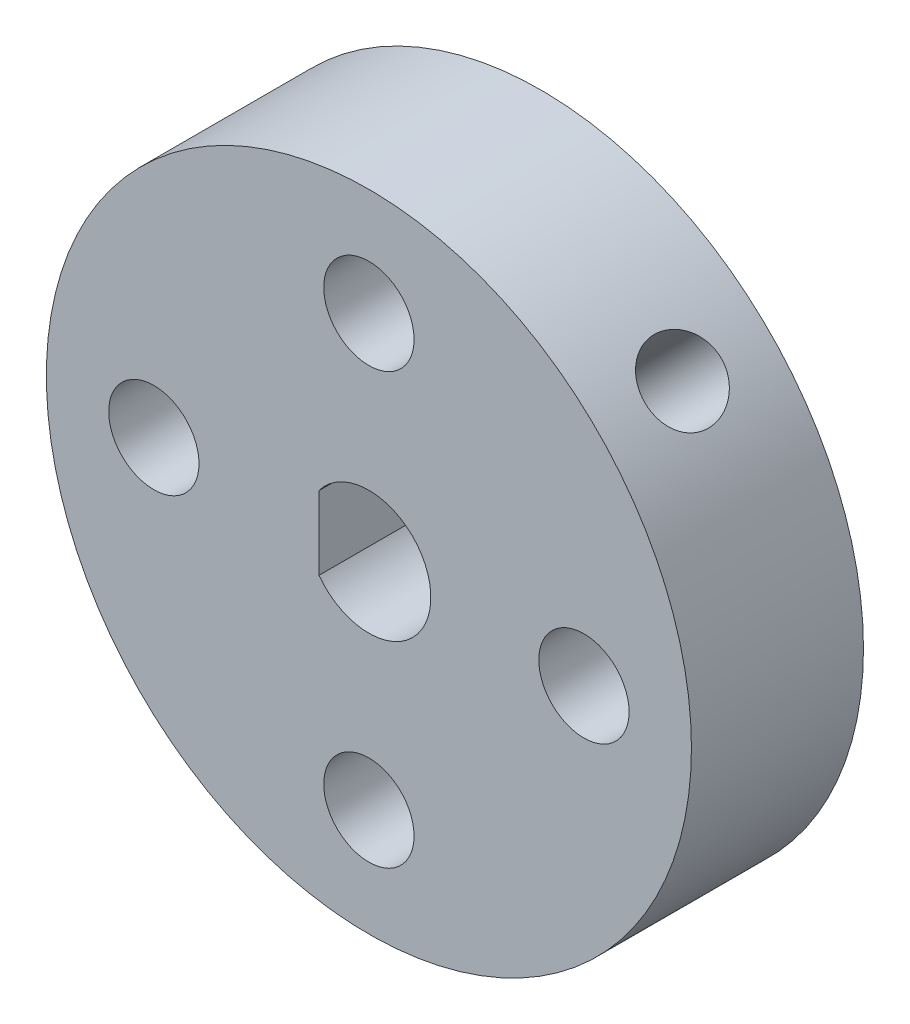
SolidWorks part; units mm, degrees
ref_plane "Front Plane" through (0, 0, 0) normal (0, 0, 1) x (1, 0, 0)
ref_plane "Top Plane" through (0, 0, 0) normal (0, 1, 0) x (1, 0, 0)
ref_plane "Right Plane" through (0, 0, 0) normal (1, 0, 0) x (0, 0, -1)
sketch "Sketch1" plane through (0, 0, 0) normal (0, 0, 1) x (1, 0, 0)
  line L0 (0, 0) -> (6.7352, 6.7352) construction
  line L1 (6.7352, 6.7352) -> (6.35, 0) construction
  line L2 (6.35, 0) -> (6.7352, 6.7352) construction
  line L3 (6.7352, 6.7352) -> (0, 6.35) construction
  line L4 (-1.4732, 1.0836) -> (-1.4732, -1.0836)
  circle A0 centre (0, 0) radius 9.525
  arc A1 (-1.4732, -1.0836) -> (-1.4732, 1.0836) centre (0, 0) ccw
  circle A2 centre (-6.35, 0) radius 1.3335
  circle A3 centre (0, 6.35) radius 1.3335
  circle A4 centre (6.35, 0) radius 1.3335
  circle A5 centre (0, -6.35) radius 1.3335
  point P3 (0, 0)
  point P15 (1.8288, 0)
  dimension "D1" = 19.05
  dimension "D2" = 3.6576
  dimension "D4" = 2.667
  dimension "D3" = 6.35
  dimension "D6" = 3.302
  dimension "D5" = 4
extrude "Boss-Extrude1" add sketch "Sketch1" along normal blind 5.08
ref_plane "Plane1" through (6.7352, 6.7352, 0) normal (0.7071, 0.7071, 0) x (-0.7071, 0.7071, 0)
sketch "Sketch2" plane through (6.7352, 6.7352, 0) normal (0.7071, 0.7071, 0) x (-0.7071, 0.7071, 0)
  circle A0 centre (0, 2.54) radius 1.1303
  dimension "D1" = 2.2606
  dimension "D2" = 2.54
extrude "Cut-Extrude1" cut sketch "Sketch2" against normal blind 10.16
